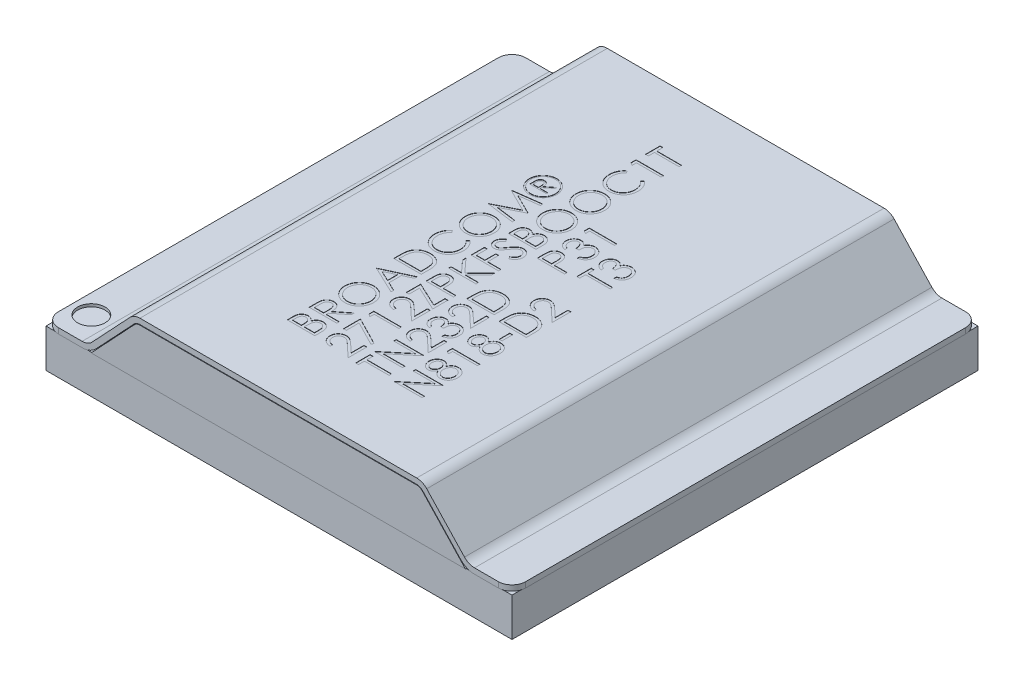
SolidWorks part; units mm, degrees
ref_plane "Płaszczyzna przednia" through (0, 0, 0) normal (0, 0, 1) x (1, 0, 0)
ref_plane "Płaszczyzna górna" through (0, 0, 0) normal (0, 1, 0) x (1, 0, 0)
ref_plane "Płaszczyzna prawa" through (0, 0, 0) normal (1, 0, 0) x (0, 0, -1)
sketch "Szkic1" plane through (0, 0, 0) normal (0, 0, 1) x (1, 0, 0)
  line L0 (8.5, -1.78) -> (8.5, -1.58)
  line L1 (8.5, -1.78) -> (7.1365, -1.78)
  line L2 (6.626, -1.5589) -> (5.2523, -0.0947)
  line L3 (5.0335, 0) -> (-5.0335, 0)
  line L4 (-5.2523, -0.0947) -> (-6.626, -1.5589)
  line L5 (-7.1365, -1.78) -> (-8.5, -1.78)
  line L6 (-8.5, -1.78) -> (-8.5, -1.58)
  line L7 (8.5, -1.58) -> (7.1365, -1.58)
  line L8 (6.7719, -1.4221) -> (5.3981, 0.0421)
  line L9 (5.0335, 0.2) -> (-5.0335, 0.2)
  line L10 (-5.3981, 0.0421) -> (-6.7719, -1.4221)
  line L11 (-7.1365, -1.58) -> (-8.5, -1.58)
  line L14 (0, 0) -> (0, -2.1595) construction
  line L15 (0, 0) -> (0, -1.08) construction
  arc A0 (7.1365, -1.78) -> (6.626, -1.5589) centre (7.1365, -1.08) cw
  arc A1 (5.2523, -0.0947) -> (5.0335, 0) centre (5.0335, -0.3) ccw
  arc A2 (-5.0335, 0) -> (-5.2523, -0.0947) centre (-5.0335, -0.3) ccw
  arc A3 (-6.626, -1.5589) -> (-7.1365, -1.78) centre (-7.1365, -1.08) cw
  arc A4 (7.1365, -1.58) -> (6.7719, -1.4221) centre (7.1365, -1.08) cw
  arc A5 (5.3981, 0.0421) -> (5.0335, 0.2) centre (5.0335, -0.3) ccw
  arc A6 (-5.0335, 0.2) -> (-5.3981, 0.0421) centre (-5.0335, -0.3) ccw
  arc A7 (-6.7719, -1.4221) -> (-7.1365, -1.58) centre (-7.1365, -1.08) cw
  dimension "D1" = 0.2
  dimension "D2" = 0.2
extrude "Dodanie-wyciągnięcie1" add sketch "Szkic1" along normal blind 17
fillet "Zaokrąglenie1" radius 0.5 4 edges at (-8.5, -1.68, 0) (8.5, -1.68, 0) (-8.5, -1.68, 17) (8.5, -1.68, 17)
sketch "Szkic2" plane through (0, -1.78, 0) normal (0, -1, 0) x (1, 0, 0)
  line L0 (-8.5, 8.5) -> (8.5, 8.5) construction
  line L1 (-8.5, 16.5) -> (-8.5, 0.5) construction
  line L2 (8.5, 16.5) -> (8.5, 0.5) construction
  line L4 (-8.475, 0.025) -> (8.475, 0.025)
  line L5 (-8.475, 0.025) -> (-8.475, 16.975)
  line L6 (-8.475, 16.975) -> (8.475, 16.975)
  line L7 (8.475, 0.025) -> (8.475, 16.975)
  line L8 (-8.475, 0.025) -> (8.475, 16.975) construction
  line L9 (-8.475, 16.975) -> (8.475, 0.025) construction
  point P6 (0, 8.5)
  dimension "D1" = 16.95
extrude "Dodanie-wyciągnięcie2" add sketch "Szkic2" along normal blind 1.4 separate body
sketch "Szkic3" plane through (0, 0, 17) normal (0, 0, 1) x (1, 0, 0)
  line L3 (8.475, -1.78) -> (-8.475, -1.78) construction
  line L4 (-6.806, -1.78) -> (6.806, -1.78)
  line L6 (5.2377, -0.1084) -> (6.6114, -1.5726)
  line L7 (-5.0335, -0.02) -> (5.0335, -0.02)
  line L8 (-6.6114, -1.5726) -> (-5.2377, -0.1084)
  line L9 (5.2377, -0.1084) -> (6.806, -1.78)
  line L10 (-5.0335, -0.02) -> (5.0335, -0.02)
  line L11 (-6.806, -1.78) -> (-5.2377, -0.1084)
  arc A4 (5.2377, -0.1084) -> (5.0335, -0.02) centre (5.0335, -0.3) ccw
  arc A5 (-5.0335, -0.02) -> (-5.2377, -0.1084) centre (-5.0335, -0.3) ccw
  arc A6 (5.2377, -0.1084) -> (5.0335, -0.02) centre (5.0335, -0.3) ccw
  arc A7 (-5.0335, -0.02) -> (-5.2377, -0.1084) centre (-5.0335, -0.3) ccw
  dimension "D1" = 0.02
extrude "Dodanie-wyciągnięcie3" add sketch "Szkic3" against normal blind 1 separate body
ref_plane "Płaszczyzna1" through (0, 0, 8.5) normal (0, 0, -1) x (-1, 0, 0)
mirror "Lustro1" about plane through (0, 0, 8.5) normal (0, 0, -1) of bodies 103
sketch "Szkic4" plane through (0, -1.58, 0) normal (0, 1, 0) x (1, 0, 0)
  line L0 (-8.5, -16.5) -> (-8.5, -0.5) construction
  line L1 (-7.1365, -17) -> (-8, -17) construction
  circle A0 centre (-7.8, -16) radius 0.5
  dimension "D1" = 0.7
  dimension "D2" = 1
  dimension "D3" = 1
extrude "Wytnij-wyciągnięcie1" cut sketch "Szkic4" against normal blind 0.1
sketch "Szkic5" plane through (0, 0.2, 0) normal (0, 1, 0) x (1, 0, 0)
  line L0 (0, -14.5) -> (0, 0) construction
  line L1 (-1.5709, -5.7623) -> (-1.5709, -5.1997) construction
  line L3 (-1.3, -14.5) -> (-1.3, -2.0364) construction
  line L4 (1.3, -14.5) -> (1.3, -2.0364) construction
  line L5 (2.6, -14.5) -> (2.6, -2.0364) construction
  circle A0 centre (-1.8427, -5.5199) radius 0.5 construction
  circle A1 centre (-1.8427, -5.5199) radius 0.42 construction
  text T0 "2712ZPKFSBOOC1T" font "Century Gothic" height 1
  text T1 "BROADCOM " font "Century Gothic" height 1
  text T2 "TN232D    P31" font "Century Gothic" height 1
  text T3 "N818-D2   T3" font "Century Gothic" height 1
  text T4 "R" font "Century Gothic" height 0.6
  dimension "D6" = 1
  dimension "D5" = 0.08
extrude "Wytnij-wyciągnięcie2" cut sketch "Szkic5" against normal blind 0.01
sketch "Szkic6" plane through (0, 0.2, 0) normal (0, 1, 0) x (1, 0, 0)
  circle A0 centre (-1.8478, -5.5212) radius 0.45
  circle A1 centre (-1.8478, -5.5212) radius 0.5
  dimension "D1" = 0.9
  dimension "D2" = 0.05
extrude "Wytnij-wyciągnięcie3" cut sketch "Szkic6" against normal blind 0.01
